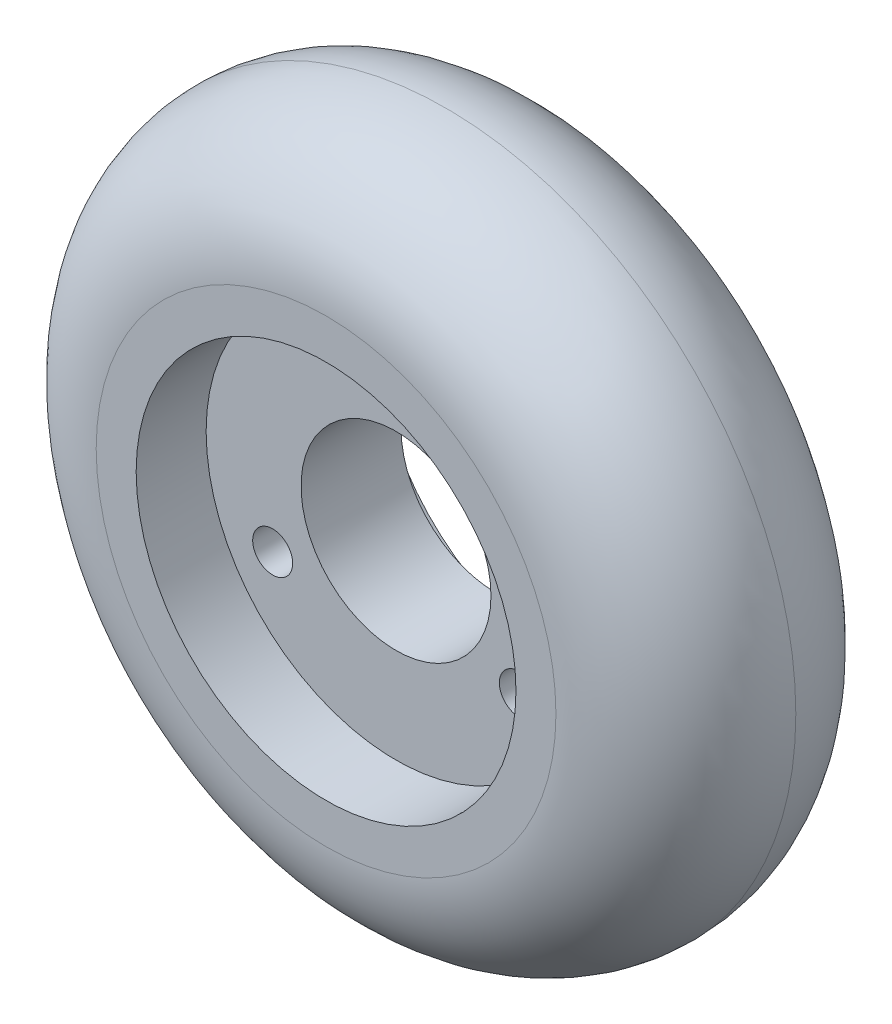
SolidWorks part; units mm, degrees
ref_plane "Face" through (0, 0, 0) normal (0, 0, 1) x (1, 0, 0)
ref_plane "Dessus" through (0, 0, 0) normal (0, 1, 0) x (1, 0, 0)
ref_plane "Droite" through (0, 0, 0) normal (1, 0, 0) x (0, 0, -1)
sketch "Esquisse1" plane through (0, 0, 0) normal (0, 0, 1) x (1, 0, 0)
  circle A0 centre (0, 0) radius 35
  dimension "D1" = 70
extrude "Extrusion1" add sketch "Esquisse1" along normal blind 24
fillet "Congé1" radius 12 1 edges at (35, 0, 24)
fillet "Congé2" radius 12 1 edges at (35, 0, 0)
sketch "Esquisse2" plane through (0, 0, 24) normal (0, 0, 1) x (1, 0, 0)
  circle A0 centre (0, 0) radius 19
  dimension "D1" = 38
extrude "Enlèv. mat.-Extru.1" cut sketch "Esquisse2" against normal blind 7
sketch "Esquisse3" plane through (0, 0, 0) normal (0, 0, -1) x (-1, 0, 0)
  circle A0 centre (0, 0) radius 19
  dimension "D1" = 38
extrude "Enlèv. mat.-Extru.2" cut sketch "Esquisse3" against normal blind 7
sketch "Esquisse5" plane through (0, 0, 17) normal (0, 0, 1) x (1, 0, 0)
  circle A0 centre (0, 0) radius 9.5
  circle A2 centre (0, 14.25) radius 2
  circle A3 centre (12.3409, -7.125) radius 2
  circle A4 centre (-12.3409, -7.125) radius 2
  dimension "D1" = 19
  dimension "D2" = 14.25
extrude "Enlèv. mat.-Extru.3" cut sketch "Esquisse5" against normal through all
sketch "Esquisse6" plane through (0, 0, 17) normal (0, 0, 1) x (1, 0, 0)
  line L0 (0, 0) -> (0, 19) construction
  line L1 (0, 0) -> (16.4545, -9.5) construction
  line L2 (0, 0) -> (-16.4545, -9.5) construction
  circle A0 centre (0, 0) radius 19 construction
  circle A1 centre (0, 0) radius 19 construction
  dimension "D1" = 120
  dimension "D2" = 120
